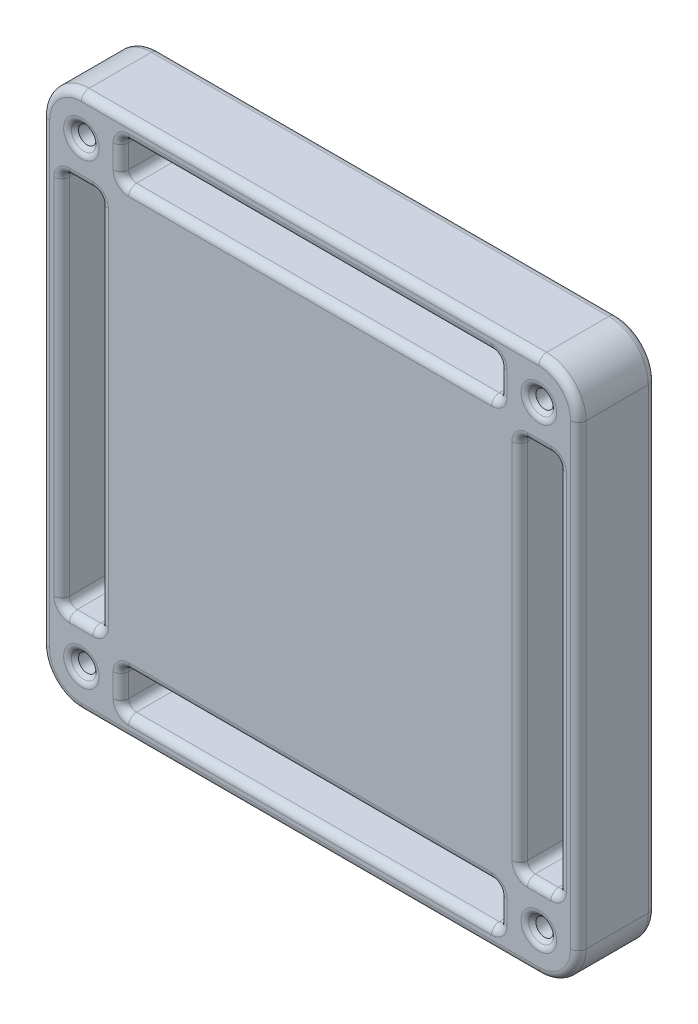
SolidWorks part; units mm, degrees
note: '?' marks a value the reader was unsure of.
ref_plane "Front Plane" through (0, 0, 0) normal (1, 0, 0) x (0, 1, 0)
ref_plane "Top Plane" through (0, 0, 0) normal (0, 0, 1) x (0, 1, 0)
ref_plane "Right Plane" through (0, 0, 0) normal (0, 1, 0) x (-1, 0, 0)
sketch "Sketch1" plane through (0, 0, 0) normal (0, 0, 1) x (0, 1, 0)
  line L1 (0, 0) -> (69, 0)
  line L2 (0, 0) -> (0, -69)
  line L3 (0, -69) -> (69, -69)
  line L4 (69, 0) -> (69, -69)
  point P4 (0, 0)
  dimension "D1" = 69
  dimension "D2" = 69
extrude "Boss-Extrude1" add sketch "Sketch1" along normal blind 10
fillet "Fillet1" radius 5.08 4 edges at (0, 0, 5) (0, 69, 5) (69, 69, 5) (69, 0, 5)
sketch "Sketch3" plane through (0, 0, 10) normal (0, 0, 1) x (1, 0, 0)
  line L1 (2.54, 58.84) -> (7.54, 58.84)
  line L2 (2.54, 58.84) -> (2.54, 10.16)
  line L3 (2.54, 10.16) -> (7.54, 10.16)
  line L4 (7.54, 58.84) -> (7.54, 10.16)
  line L17 (0, 63.92) -> (0, 5.08) construction
  circle A0 centre (5.08, 63.92) radius 1.125
  point P3 (5.08, 5.08)
  dimension "D1" = 2.25
  dimension "D2" = 5.08
  dimension "D3" = 2.54
  dimension "D8" = 5
  dimension "D14" = 5.08
extrude "Cut-Extrude1" cut sketch "Sketch3" against normal blind 10
chamfer "Chamfer1" distance 0.75 angle 45 2 edges at (6.205, 63.92, 0) (6.205, 63.92, 10)
fillet "Fillet2" radius 1 30 edges at (5.04, 10.16, 10) (7.54, 34.5, 10) (5.04, 58.84, 10) (2.54, 34.5, 10) (67.5121, 1.4879, 0) (69, 34.5, 0) (67.5121, 67.5121, 0) (34.5, 69, 0) (1.4879, 67.5121, 0) (0, 34.5, 0) (1.4879, 1.4879, 0) (34.5, 0, 0) (5.04, 10.16, 0) (2.54, 34.5, 0) (5.04, 58.84, 0) (7.54, 34.5, 0) (6.955, 63.92, 0) (1.4879, 67.5121, 10) (34.5, 69, 10) (67.5121, 67.5121, 10) (69, 34.5, 10) (67.5121, 1.4879, 10) (34.5, 0, 10) (1.4879, 1.4879, 10) (0, 34.5, 10) (6.955, 63.92, 10) (2.54, 10.16, 5) (7.54, 10.16, 5) (7.54, 58.84, 5) (2.54, 58.84, 5)
sketch "Sketch5" plane through (0, 0, 10) normal (0, 0, 1) x (1, 0, 0)
  line L0 (34.5, 68) -> (34.5, 1) construction
  line L1 (63.92, 68) -> (5.08, 68) construction
  line L2 (5.08, 1) -> (63.92, 1) construction
  line L3 (68, 34.5) -> (1, 34.5) construction
  line L4 (68, 5.08) -> (68, 63.92) construction
  line L5 (1, 63.92) -> (1, 5.08) construction
  point P12 (34.5, 34.5)
ref_axis "Axis1" through (34.5, 34.5, 10) along (0, 0, 1)?
pattern_circular "CirPattern1" count 4 every 90 about axis through (34.5, 34.5, 10) along (0, 0, 1) of "Cut-Extrude1", "Chamfer1", "Fillet2"
sketch "Sketch7" plane through (0, 0, 0) normal (0, 0, 1) x (0, 1, 0)
  line L0 (0.0711, -68.6697) -> (68.6511, -68.6697) construction
  dimension "D1" = 68.58
